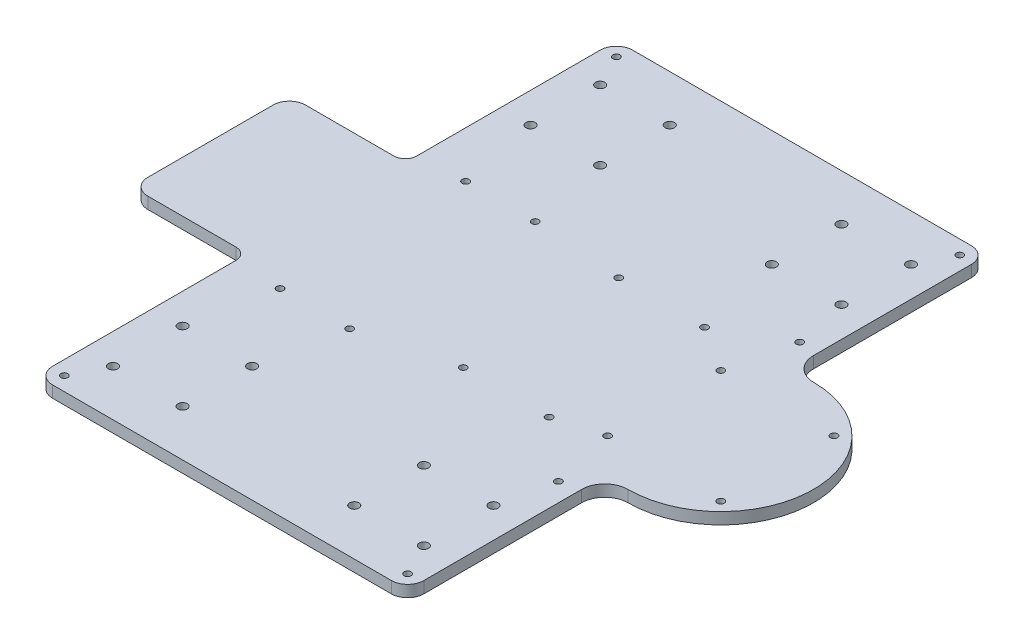
SolidWorks part; units mm, degrees
ref_plane "前视基准面" through (0, 0, 0) normal (0, 0, 1) x (1, 0, 0)
ref_plane "上视基准面" through (0, 0, 0) normal (0, 1, 0) x (1, 0, 0)
ref_plane "右视基准面" through (0, 0, 0) normal (1, 0, 0) x (0, 0, -1)
other "Configuration Table"
sketch "草图1" plane through (0, 0, 0) normal (0, 1, 0) x (1, 0, 0)
  line L0 (-10, -125) -> (170, -125) construction
  line L1 (0, 0) -> (160, 0)
  line L2 (0, 0) -> (0, -91)
  line L3 (0, -250) -> (160, -250)
  line L4 (160, 0) -> (160, -85)
  line L9 (80, 0) -> (80, -125) construction
  line L13 (0, -159) -> (0, -250)
  line L14 (160, -165) -> (160, -250)
  line L15 (170, -85) -> (160, -85)
  line L20 (170, -165) -> (160, -165)
  line L21 (75, -75) -> (140, -75) construction
  line L26 (107.5, -125) -> (107.5, -121.5) construction
  line L28 (0, -91) -> (-50, -91)
  line L33 (75, -75) -> (75, -175) construction
  line L34 (75, -175) -> (140, -175) construction
  line L38 (-50, -159) -> (-50, -91)
  line L39 (140, -75) -> (140, -175) construction
  line L40 (75, -75) -> (140, -175) construction
  line L41 (0, -159) -> (-50, -159)
  line L42 (75, -175) -> (140, -75) construction
  line L43 (80, -125) -> (80, -244) construction
  line L44 (13, -20) -> (43, -20) construction
  line L45 (13, -20) -> (13, -50) construction
  line L46 (13, -50) -> (43, -50) construction
  line L47 (43, -20) -> (43, -50) construction
  line L48 (13, -200) -> (43, -200) construction
  line L49 (13, -200) -> (13, -230) construction
  line L50 (13, -230) -> (43, -230) construction
  line L51 (43, -200) -> (43, -230) construction
  line L53 (20, -85) -> (50, -85) construction
  line L54 (20, -85) -> (20, -165) construction
  line L55 (20, -165) -> (50, -165) construction
  line L56 (50, -85) -> (50, -165) construction
  line L60 (145.605, -100.605) -> (194.395, -100.605) construction
  line L61 (145.605, -100.605) -> (145.605, -149.395) construction
  line L62 (89, -88) -> (126, -88) construction
  line L63 (89, -88) -> (89, -155) construction
  line L64 (89, -155) -> (126, -155) construction
  line L65 (126, -88) -> (126, -155) construction
  line L66 (89, -88) -> (126, -155) construction
  line L67 (89, -155) -> (126, -88) construction
  line L68 (145.605, -149.395) -> (194.395, -149.395) construction
  line L71 (194.395, -100.605) -> (194.395, -149.395) construction
  line L74 (145.605, -100.605) -> (194.395, -149.395) construction
  line L75 (145.605, -149.395) -> (194.395, -100.605) construction
  circle A0 centre (154, -6) radius 1.5
  circle A2 centre (6, -6) radius 1.5
  circle A9 centre (8, -76) radius 1.5 construction
  circle A20 centre (152, -73) radius 1.5
  circle A35 centre (152, -177) radius 1.5
  circle A38 centre (154, -244) radius 1.5
  circle A40 centre (6, -244) radius 1.5
  circle A42 centre (8, -174) radius 1.5 construction
  circle A48 centre (50, -85) radius 1.5
  circle A49 centre (50, -165) radius 1.5
  circle A50 centre (80, -6) radius 1.5 construction
  circle A52 centre (13, -20) radius 2
  circle A60 centre (13, -200) radius 2
  circle A68 centre (20, -85) radius 1.5
  circle A69 centre (20, -165) radius 1.5
  circle A70 centre (80, -244) radius 1.5 construction
  circle A72 centre (89, -88) radius 1.5
  circle A77 centre (126, -88) radius 1.5
  circle A78 centre (126, -155) radius 1.5
  circle A79 centre (89, -155) radius 1.5
  circle A104 centre (43, -200) radius 2
  circle A105 centre (13, -230) radius 2
  circle A106 centre (43, -230) radius 2
  circle A107 centre (117, -230) radius 2
  circle A108 centre (147, -230) radius 2
  circle A109 centre (117, -200) radius 2
  circle A110 centre (147, -200) radius 2
  circle A112 centre (43, -20) radius 2
  circle A113 centre (13, -50) radius 2
  circle A114 centre (43, -50) radius 2
  circle A115 centre (117, -20) radius 2
  circle A116 centre (117, -50) radius 2
  circle A117 centre (147, -50) radius 2
  circle A118 centre (147, -20) radius 2
  circle A120 centre (145.605, -100.605) radius 1.5
  circle A121 centre (194.395, -100.605) radius 1.5
  circle A122 centre (194.395, -149.395) radius 1.5
  circle A123 centre (145.605, -149.395) radius 1.5
  arc A124 (170, -165) -> (170, -85) centre (170, -125) ccw
  point P14 (107.5, -125)
  point P42 (107.5, -125)
  point P64 (170, -125)
  point P65 (170, -125)
  dimension "D4" = 3
  dimension "D7" = 6
  dimension "D9" = 65
  dimension "D11" = 3
  dimension "D13" = 48.79
  dimension "D17" = 48.79
  dimension "D20" = 3
  dimension "D24" = 67
  dimension "D19" = 4
  dimension "D18" = 3
  dimension "D37" = 20
  dimension "D39" = 4
  dimension "D42" = 3
  dimension "D45" = 3
  dimension "D50" = 4
  dimension "D55" = 4
  dimension "D29" = 3
  dimension "D12" = 10
  dimension "D26" = 3
  dimension "D31" = 4
  dimension "D34" = 4
  dimension "D56" = 4
  dimension "D40" = 4
  dimension "D57" = 4
  dimension "D10" = 80
  dimension "180" = 160
  dimension "D2" = 250
  dimension "D5" = 6
  dimension "D6" = 6
  dimension "D8" = 70
  dimension "D14" = 50
  dimension "D15" = 100
  dimension "D16" = 40
  dimension "D21" = 73
  dimension "D23" = 3.5
  dimension "D27" = 2
  dimension "D28" = 2
  dimension "D30" = 68
  dimension "D32" = 30
  dimension "D33" = 8
  dimension "D35" = 8
  dimension "D36" = 20
  dimension "D38" = 13
  dimension "D46" = 30
  dimension "D47" = 30
  dimension "D48" = 20
  dimension "D49" = 13
  dimension "D53" = 30
  dimension "D54" = 30
  dimension "D25" = 37
  dimension "D52" = 70
extrude "凸台-拉伸1" add sketch "草图1" along normal blind 5
fillet "圆角1" radius 7 6 edges at (160, 2.5, 0) (160, 2.5, 250) (0, 2.5, 0) (-50, 2.5, 91) (-50, 2.5, 159) (0, 2.5, 250)
fillet "圆角4" radius 5 2 edges at (0, 2.5, 91) (0, 2.5, 159)
fillet "圆角6" radius 10 2 edges at (160, 2.5, 85) (160, 2.5, 165)
